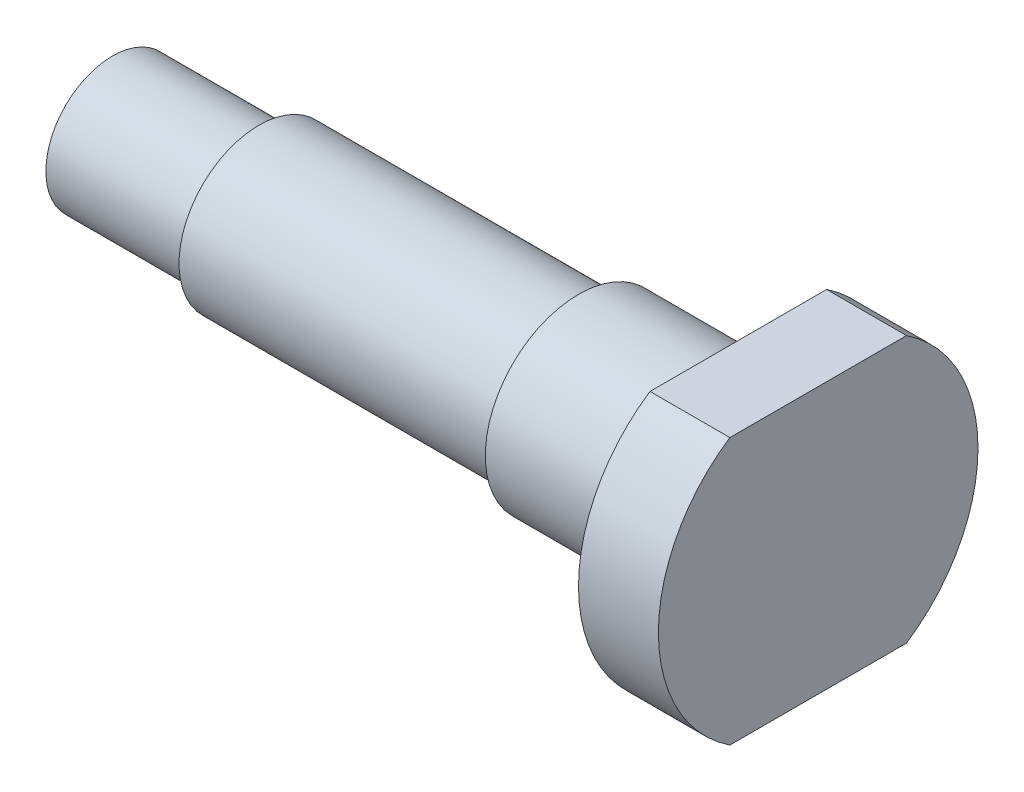
SolidWorks part; units mm, degrees
material "201 Annealed Stainless Steel (SS)"
ref_plane "Front Plane" through (0, 0, 0) normal (0, 0, 1) x (1, 0, 0)
ref_plane "Top Plane" through (0, 0, 0) normal (0, 1, 0) x (1, 0, 0)
ref_plane "Right Plane" through (0, 0, 0) normal (1, 0, 0) x (0, 0, -1)
sketch "Sketch2" plane through (0, 0, 0) normal (1, 0, 0) x (0, 0, -1)
  line L0 (-3.3166, 5) -> (3.3166, 5)
  line L1 (0, 0) -> (-50000, 0) construction
  line L2 (-3.3166, -5) -> (3.3166, -5)
  arc A0 (-3.3166, 5) -> (-3.3166, -5) centre (0, 0) ccw
  circle A1 centre (0, 0) radius 3
  circle A2 centre (0, 0) radius 2.5
  arc A3 (3.3166, -5) -> (3.3166, 5) centre (0, 0) ccw
  circle A4 centre (0, 0) radius 3.5
  dimension "D1" = 12
  dimension "D2" = 6
  dimension "D3" = 5
  dimension "D5" = 7
  dimension "D4" = 10
extrude "Boss-Extrude1" add sketch "Sketch2" along normal blind 3 contours L1 A3 L0 A0 A1 | A3 L1 A1 A0 L2 | A4 L1 A1 | L1 A4 A1 | L1 A1 A2 | A1 L1 A2 | A2 L1 | L1 A2 region at (0, 2.4293, 0) region at (0, 2.9151, 0) region at (0, 3.401, 0) region at (0, 4.8438, 0)
extrude "Boss-Extrude2" add sketch "Sketch2<4>" against normal blind 18 contours L1 A1 A2 | A1 L1 A2 region at (0, 2.9151, 0)
sketch "Sketch2<4>" plane through (0, 0, 0) normal (1, 0, 0) x (0, 0, -1) same geometry as "Sketch2"
extrude "Boss-Extrude3" add sketch "Sketch2<5>" against normal blind 23.5 contours A2 L1 | L1 A2 region at (0, 2.4293, 0)
sketch "Sketch2<5>" plane through (0, 0, 0) normal (1, 0, 0) x (0, 0, -1) same geometry as "Sketch2"
cosmetic thread "Cosmetic Thread1" parameters "D2"=3.22
extrude "Boss-Extrude4" add sketch "Sketch2<6>" against normal blind 6 contours L1 A4 A1 | A4 L1 A1 region at (0, 3.401, 0)
sketch "Sketch2<6>" plane through (0, 0, 0) normal (1, 0, 0) x (0, 0, -1) same geometry as "Sketch2"
